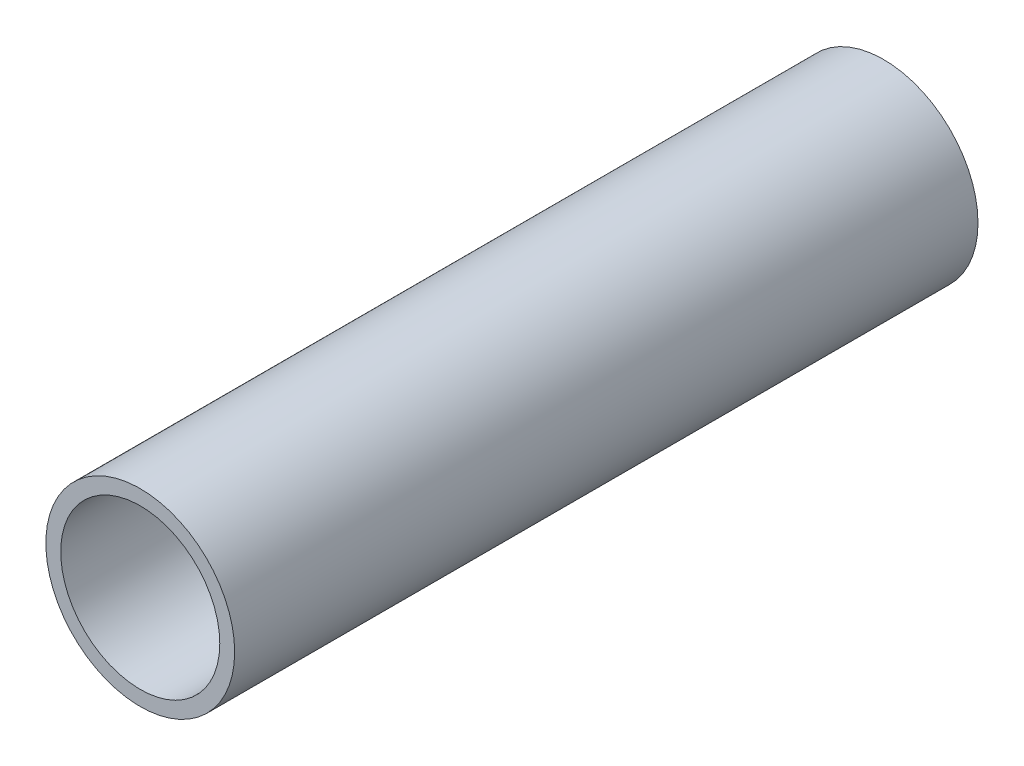
SolidWorks part; units mm, degrees
material "Hexcel AS4C (3000 Filaments)"
ref_plane "Front Plane" through (0, 0, 0) normal (0, 0, 1) x (1, 0, 0)
ref_plane "Top Plane" through (0, 0, 0) normal (0, 1, 0) x (1, 0, 0)
ref_plane "Right Plane" through (0, 0, 0) normal (1, 0, 0) x (0, 0, -1)
sketch "Sketch1" plane through (0, 0, 0) normal (0, 0, 1) x (1, 0, 0)
  circle A0 centre (0, 0) radius 12.7
  circle A1 centre (0, 0) radius 10.7
  dimension "D1" = 25.4
  dimension "D2" = 2
extrude "Boss-Extrude1" add sketch "Sketch1" along normal blind 100
